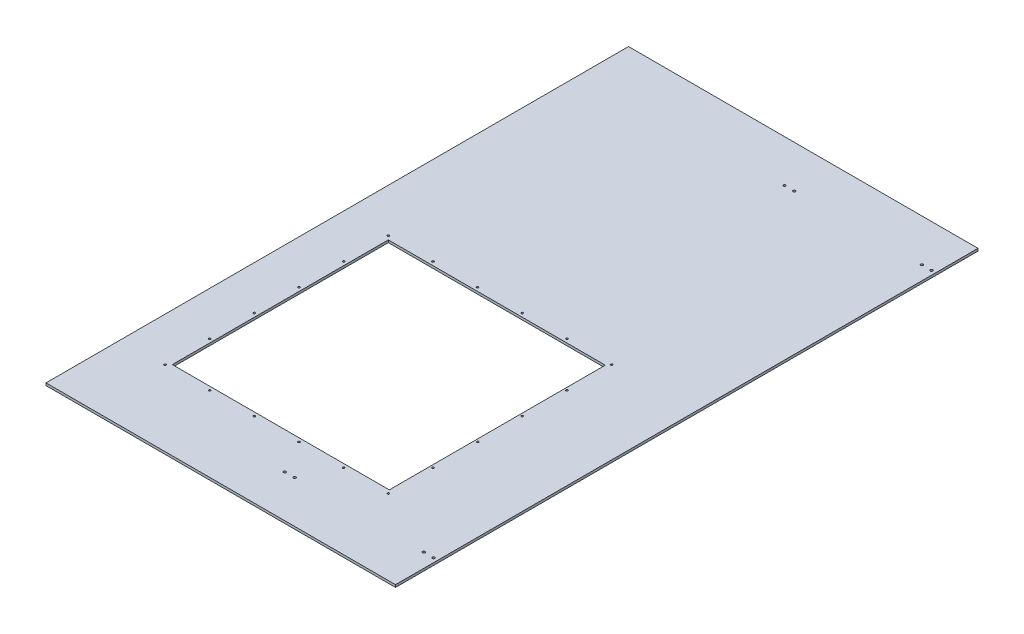
SolidWorks part; units mm, degrees
ref_plane "Front Plane" through (0, 0, 0) normal (0, 0, 1) x (1, 0, 0)
ref_plane "Top Plane" through (0, 0, 0) normal (0, 1, 0) x (1, 0, 0)
ref_plane "Right Plane" through (0, 0, 0) normal (1, 0, 0) x (0, 0, -1)
sketch "Sketch1" plane through (0, 0, 0) normal (0, 1, 0) x (1, 0, 0)
  line L1 (-457.2, -762) -> (457.2, -762)
  line L2 (-457.2, -762) -> (-457.2, 762)
  line L3 (-457.2, 762) -> (457.2, 762)
  line L4 (457.2, -762) -> (457.2, 762)
  line L5 (-457.2, -762) -> (457.2, 762) construction
  line L6 (-457.2, 762) -> (457.2, -762) construction
  point P0 (0, 0)
  dimension "D1" = 1524
  dimension "D2" = 914.4
extrude "Boss-Extrude1" add sketch "Sketch1" along normal blind 6.35
sketch "Sketch2" plane through (0, 0, 0) normal (0, -1, 0) x (1, 0, 0)
  line L0 (457.2, 762) -> (457.2, -762) construction
  circle A4 centre (56.9595, 651.2814) radius 3.2639
  circle A5 centre (82.3595, 651.2814) radius 3.2639
  circle A6 centre (446.0875, 651.2814) radius 3.2639
  circle A7 centre (420.6875, 651.2814) radius 3.2639
  circle A12 centre (61.722, -651.2814) radius 3.2639
  circle A13 centre (87.122, -651.2814) radius 3.2639
  circle A14 centre (420.878, -651.2814) radius 3.2639
  circle A15 centre (446.278, -651.2814) radius 3.2639
  dimension "D1" = 6.5278
  dimension "D2" = 10.922
  dimension "D3" = 11.1125
  dimension "D4" = 36.322
  dimension "D5" = 36.5125
  dimension "D6" = 370.078
  dimension "D7" = 374.8405
  dimension "D8" = 395.478
  dimension "D9" = 400.2405
  dimension "D10" = 110.7186
  dimension "D11" = 1413.2814
extrude "Cut-Extrude1" cut sketch "Sketch2" against normal through all
sketch "Sketch3" plane through (0, 6.35, 0) normal (0, 1, 0) x (1, 0, 0)
  line L4 (-333.375, 9.779) -> (-333.375, -555.371)
  line L13 (-342.9, 19.304) -> (243.8908, 19.304) construction
  line L14 (-342.9, 19.304) -> (-342.9, -564.896) construction
  line L15 (-342.9, -564.896) -> (243.8908, -564.896) construction
  line L16 (243.8908, 19.304) -> (243.8908, -564.896) construction
  line L18 (-333.375, -555.371) -> (234.3658, -555.371)
  line L19 (234.3658, 9.779) -> (234.3658, -555.371)
  line L20 (-333.375, 9.779) -> (234.3658, 9.779)
  circle A2 centre (241.3, 19.304) radius 2.5908
  circle A4 centre (241.3, -97.536) radius 2.5908
  circle A6 centre (241.3, -214.376) radius 2.5908
  circle A8 centre (241.3, -331.216) radius 2.5908
  circle A10 centre (241.3, -448.056) radius 2.5908
  circle A12 centre (241.3, -564.896) radius 2.5908
  circle A14 centre (-342.9, -564.896) radius 2.5908
  circle A16 centre (-226.06, -564.896) radius 2.5908
  circle A18 centre (-109.22, -564.896) radius 2.5908
  circle A20 centre (7.62, -564.896) radius 2.5908
  circle A22 centre (124.46, -564.896) radius 2.5908
  circle A24 centre (-342.9, -448.056) radius 2.5908
  circle A26 centre (-342.9, -331.216) radius 2.5908
  circle A28 centre (-342.9, -214.376) radius 2.5908
  circle A30 centre (-342.9, -97.536) radius 2.5908
  circle A32 centre (124.46, 19.304) radius 2.5908
  circle A34 centre (7.62, 19.304) radius 2.5908
  circle A36 centre (-109.22, 19.304) radius 2.5908
  circle A38 centre (-226.06, 19.304) radius 2.5908
  circle A39 centre (446.0875, -651.2814) radius 3.2639 construction
  circle A40 centre (-342.9, 19.304) radius 2.5908
  dimension "D1" = 5.1816
  dimension "D2" = 204.7875
  dimension "D3" = 321.6275
  dimension "D4" = 438.4675
  dimension "D5" = 555.3075
  dimension "D6" = 672.1475
  dimension "D7" = 788.9875
  dimension "D8" = 86.3854
  dimension "D9" = 203.2254
  dimension "D10" = 320.0654
  dimension "D11" = 436.9054
  dimension "D12" = 553.7454
  dimension "D13" = 670.5854
  dimension "D14" = 9.525
extrude "Cut-Extrude2" cut sketch "Sketch3" against normal through all contours L20 L4 L18 L19 | A40 | A38 | A36 | A34 | A32 | A2 | A4 | A6 | A8 | A10 | A12 | A20 | A18 | A16 | A14 | A24 | A26 | A28 | A30 | A22 | L4 L18 L19 L20 region at (-49.5046, 6.35, 272.796) region at (241.3, 6.35, -19.304) region at (241.3, 6.35, 97.536) region at (241.3, 6.35, 214.376) region at (241.3, 6.35, 331.216) region at (241.3, 6.35, 448.056) region at (241.3, 6.35, 564.896) region at (-342.9, 6.35, 564.896) region at (-226.06, 6.35, 564.896) region at (-109.22, 6.35, 564.896) region at (7.62, 6.35, 564.896) region at (124.46, 6.35, 564.896) region at (-342.9, 6.35, 448.056) region at (-342.9, 6.35, 331.216) region at (-342.9, 6.35, 214.376) region at (-342.9, 6.35, 97.536) region at (124.46, 6.35, -19.304) region at (7.62, 6.35, -19.304) region at (-109.22, 6.35, -19.304) region at (-226.06, 6.35, -19.304) region at (-342.9, 6.35, -19.304)
